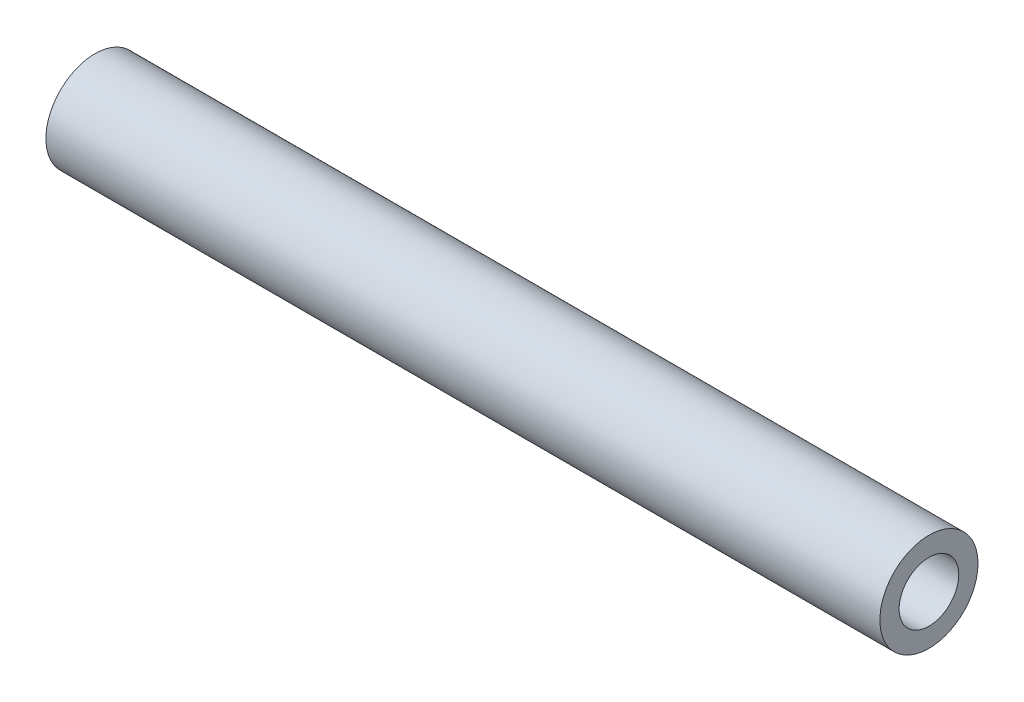
SolidWorks part; units mm, degrees
material "6061-T6 (SS)"
ref_plane "Front" through (0, 0, 0) normal (0, 0, 1) x (1, 0, 0)
ref_plane "Top" through (0, 0, 0) normal (0, 1, 0) x (1, 0, 0)
ref_plane "Right" through (0, 0, 0) normal (1, 0, 0) x (0, 0, -1)
sketch "Sketch1" plane through (0, 0, 0) normal (1, 0, 0) x (0, 0, -1)
  circle A0 centre (0, 0) radius 1.9304
  circle A1 centre (0, 0) radius 3.175
  dimension "D1" = 1.2446
  dimension "D2" = 6.35
extrude "Boss-Extrude1" add sketch "Sketch1" along normal mid plane 53.975
